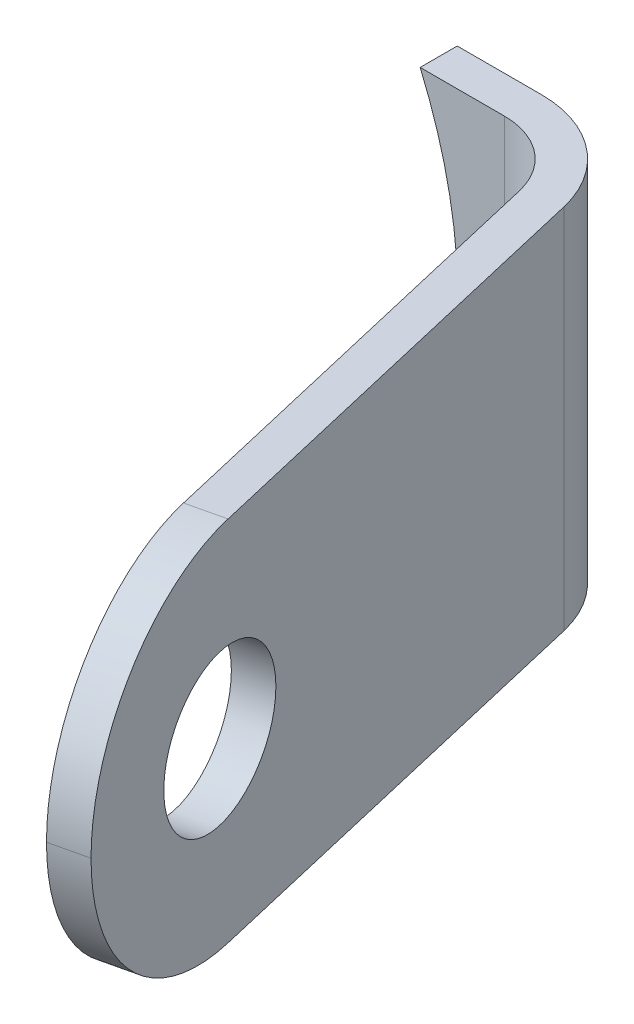
SolidWorks part; units mm, degrees
ref_plane "Front Plane" through (0, 0, 0) normal (0, 0, 1) x (1, 0, 0)
ref_plane "Top Plane" through (0, 0, 0) normal (0, 1, 0) x (1, 0, 0)
ref_plane "Right Plane" through (0, 0, 0) normal (1, 0, 0) x (0, 0, -1)
sketch "Sketch1" plane through (0, 0, 0) normal (0, 1, 0) x (1, 0, 0)
  line L0 (-15.1459, 13.5721) -> (-15.1459, 13.0641)
  line L1 (-15.1459, 13.0641) -> (-15.1121, 13.0641)
  line L2 (-11.6543, 3.943) -> (-12.149, 3.8275)
  line L3 (-15.1121, 13.5721) -> (-15.1459, 13.5721)
  line L4 (-13.628, 12.3947) -> (-11.6543, 3.943)
  line L5 (-14.1227, 12.2791) -> (-12.149, 3.8275)
  arc A0 (-15.1121, 13.0641) -> (-14.1227, 12.2791) centre (-15.1121, 12.0481) cw
  arc A1 (-15.1121, 13.5721) -> (-13.628, 12.3947) centre (-15.1121, 12.0481) cw
  dimension "D2" = 1.016
  dimension "D1" = 0.508
  dimension "D3" = 0.508
extrude "Extrude1" add sketch "Sketch1" along normal blind 2.5146 and the other way blind 2.5146
fillet "Fillet1" radius 2.5146 2 edges at (-11.9016, -2.5146, -3.8853) (-11.9016, 2.5146, -3.8853)
sketch "Sketch2" plane through (0, 0, -13.5721) normal (0, 0, -1) x (-1, 0, 0)
  line L0 (15.1459, 2.5146) -> (15.1459, -2.5146)
  line L2 (15.1459, 2.5146) -> (16.2671, 2.5146)
  line L3 (15.1459, -2.5146) -> (16.2671, -2.5146)
  arc A0 (16.2671, 2.5146) -> (16.2671, -2.5146) centre (22.098, 0) ccw
  line M3 (15.1459, -2.5146) -> (15.1459, 2.5146)
extrude "Extrude2" add sketch "Sketch2" against normal blind 0.508 contours A0 L2 M3 | A0 L0 L3 region at (-15.5473, 0, -13.5721)
hole_wizard "#97 (0.0059) Diameter Hole1" positions "3DSketch1" profile "Sketch3" hole size "#97" standard "Ansi Inch"
sketch3d "3DSketch1"
  point P0 (-12.1919, 0, -6.245)
sketch "Sketch3" plane through (-12.1919, 0, -6.245) normal (0, 1, 0) x (-0.2274, 0, -0.9738)
  line L0 (0, 0) -> (0, 6.35)
  line L1 (0, 6.35) -> (1.0287, 6.35)
  line L2 (1.0287, 6.35) -> (1.0287, 0)
  line L5 (1.0287, 0) -> (0, 0)
  line L10 (0, 6.35) -> (-1.0287, 6.35) construction
  line L11 (0, -6.35) -> (0, 107.95) construction
  dimension "Hole Dia." = 2.0574
  dimension "Hole Depth" = 6.35
  dimension "Drill Angle" = 180
